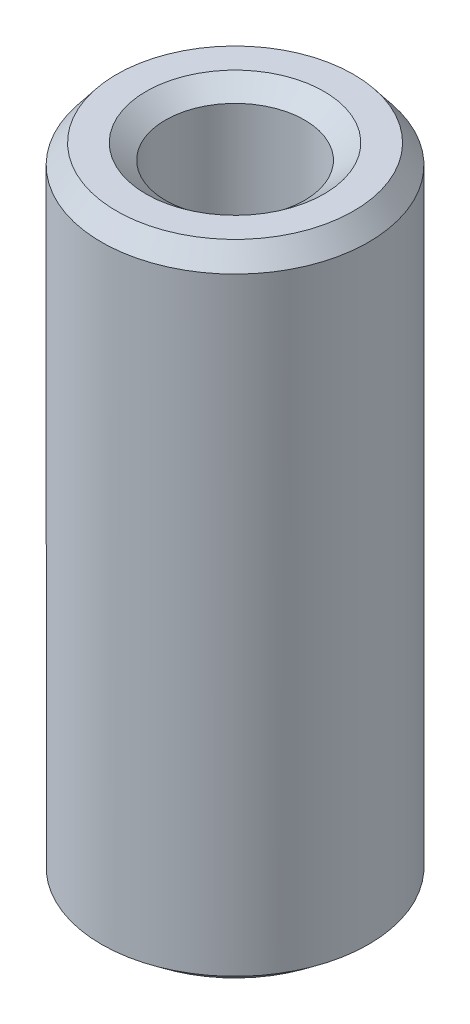
SolidWorks part; units mm, degrees
ref_plane "Front Plane" through (0, 0, 0) normal (0, 0, 1) x (1, 0, 0)
ref_plane "Top Plane" through (0, 0, 0) normal (0, 1, 0) x (1, 0, 0)
ref_plane "Right Plane" through (0, 0, 0) normal (1, 0, 0) x (0, 0, -1)
sketch "Sketch1" plane through (0, 0, 0) normal (0, 1, 0) x (1, 0, 0)
  circle A0 centre (0, 0) radius 12.5
  dimension "SLEEVE_OD" = 25
extrude "Boss-Extrude1" add sketch "Sketch1" along normal blind 60.1337
sketch "Sketch2" plane through (0, 0, 0) normal (0, 1, 0) x (1, 0, 0)
  circle A0 centre (0, 0) radius 6.5135
  dimension "BORE_D" = 13.027
extrude "Cut-Extrude1" cut sketch "Sketch2" along normal through all
chamfer "Chamfer1" distance 1.8108 angle 38.016 4 edges at (0, 60.1337, 6.5135) (0, 0, 6.5135) (0, 0, 12.5) (0, 60.1337, 12.5) first distance on face at (0, 60.1337, 6.5135) first distance on face at (0, 0, 6.5135) first distance on face at (0, 60.1337, 12.5)
